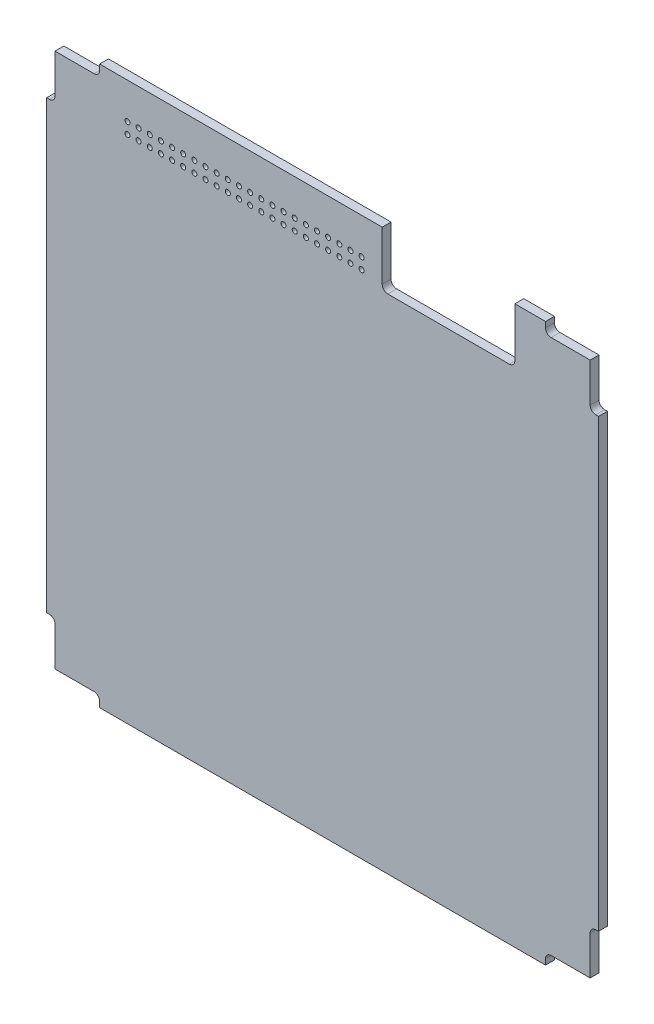
SolidWorks part; units mm, degrees
material "ABS"
ref_plane "Front Plane" through (0, 0, 0) normal (0, 0, 1) x (1, 0, 0)
ref_plane "Top Plane" through (0, 0, 0) normal (0, 1, 0) x (1, 0, 0)
ref_plane "Right Plane" through (0, 0, 0) normal (1, 0, 0) x (0, 0, -1)
sketch "Sketch1" plane through (0, 0, 0) normal (0, 0, 1) x (1, 0, 0)
  line L0 (-40, 50) -> (-40, 48)
  line L1 (-50, -50) -> (50, -50)
  line L2 (-50, -50) -> (-50, 50)
  line L3 (-50, 50) -> (50, 50)
  line L4 (50, -50) -> (50, 50)
  line L5 (-50, -50) -> (50, 50) construction
  line L6 (-50, 50) -> (50, -50) construction
  line L7 (-50, 50) -> (-40, 50)
  line L8 (-50, 50) -> (-50, 40)
  line L9 (-40, 48) -> (-48, 48)
  line L10 (-48, 48) -> (-48, 40)
  line L11 (50, 50) -> (40, 50)
  line L12 (50, 50) -> (50, 40)
  line L13 (-48, 40) -> (-50, 40)
  line L14 (50, 40) -> (48, 40)
  line L15 (-50, -50) -> (-37.8649, -50)
  line L16 (-50, -50) -> (-50, -37.8649)
  line L17 (50, 50) -> (50, 40)
  line L18 (50, 50) -> (40, 50)
  line L19 (50, -50) -> (41.5, -50)
  line L20 (50, -50) -> (50, -41.5)
  line L21 (48, 40) -> (48, 48)
  line L22 (48, 48) -> (40, 48)
  line L23 (40, 48) -> (40, 50)
  line L24 (40, -50) -> (40, -48)
  line L25 (50, -50) -> (40, -50)
  line L26 (50, -50) -> (50, -40)
  line L27 (40, -48) -> (48, -48)
  line L28 (48, -48) -> (48, -40)
  line L29 (48, -40) -> (50, -40)
  line L30 (-50, -40) -> (-48, -40)
  line L31 (-50, -50) -> (-50, -40)
  line L32 (-50, -50) -> (-40, -50)
  line L33 (-48, -40) -> (-48, -48)
  line L34 (-48, -48) -> (-40, -48)
  line L35 (-40, -48) -> (-40, -50)
  point P0 (0, 0)
  point P38 (0, 0)
  dimension "D1" = 100
  dimension "D2" = 100
  dimension "D3" = 2
  dimension "D4" = 10
  dimension "D5" = 4
extrude "Boss-Extrude1" add sketch "Sketch1" along normal blind 1.5875 contours L1 L4 L3 L2 region at (0, 0, 0)
fillet "Fillet1" radius 1 8 edges at (-48, -40, 0.7937) (-40, -48, 0.7937) (40, -48, 0.7937) (48, -40, 0.7937) (48, 40, 0.7937) (40, 48, 0.7937) (-40, 48, 0.7937) (-48, 40, 0.7937)
sketch "Sketch2" plane through (0, 0, 1.5875) normal (0, 0, 1) x (1, 0, 0)
  line L0 (0, 50) -> (0, -50) construction
  line L1 (-40, 50) -> (40, 50) construction
  line L2 (-40, -50) -> (40, -50) construction
  line L4 (-36, 45.8) -> (8, 45.8) construction
  line L5 (-36, 45.8) -> (-36, 43.55) construction
  line L6 (-36, 43.55) -> (8, 43.55) construction
  line L7 (8, 45.8) -> (8, 43.55) construction
  line L8 (-36, 50) -> (8, 50) construction
  line L9 (-36, 50) -> (-36, 45.8) construction
  line L10 (-36, 45.8) -> (8, 45.8) construction
  line L11 (8, 50) -> (8, 45.8) construction
  circle A0 centre (-35, 43.55) radius 0.45
  circle A1 centre (-33, 43.55) radius 0.45
  circle A2 centre (-31, 43.55) radius 0.45
  circle A3 centre (-29, 43.55) radius 0.45
  circle A4 centre (-27, 43.55) radius 0.45
  circle A5 centre (-25, 43.55) radius 0.45
  circle A6 centre (-23, 43.55) radius 0.45
  circle A7 centre (-21, 43.55) radius 0.45
  circle A8 centre (-19, 43.55) radius 0.45
  circle A9 centre (-17, 43.55) radius 0.45
  circle A10 centre (-15, 43.55) radius 0.45
  circle A11 centre (-13, 43.55) radius 0.45
  circle A12 centre (-11, 43.55) radius 0.45
  circle A13 centre (-9, 43.55) radius 0.45
  circle A14 centre (-7, 43.55) radius 0.45
  circle A15 centre (-5, 43.55) radius 0.45
  circle A16 centre (-3, 43.55) radius 0.45
  circle A17 centre (-1, 43.55) radius 0.45
  circle A18 centre (1, 43.55) radius 0.45
  circle A19 centre (3, 43.55) radius 0.45
  circle A20 centre (5, 43.55) radius 0.45
  circle A21 centre (7, 43.55) radius 0.45
  circle A22 centre (-33, 41.55) radius 0.45
  circle A23 centre (-31, 41.55) radius 0.45
  circle A24 centre (-29, 41.55) radius 0.45
  circle A25 centre (-27, 41.55) radius 0.45
  circle A26 centre (-25, 41.55) radius 0.45
  circle A27 centre (-23, 41.55) radius 0.45
  circle A28 centre (-21, 41.55) radius 0.45
  circle A29 centre (-19, 41.55) radius 0.45
  circle A30 centre (-17, 41.55) radius 0.45
  circle A31 centre (-15, 41.55) radius 0.45
  circle A32 centre (-13, 41.55) radius 0.45
  circle A33 centre (-11, 41.55) radius 0.45
  circle A34 centre (-9, 41.55) radius 0.45
  circle A35 centre (-7, 41.55) radius 0.45
  circle A36 centre (-5, 41.55) radius 0.45
  circle A37 centre (-3, 41.55) radius 0.45
  circle A38 centre (-1, 41.55) radius 0.45
  circle A39 centre (1, 41.55) radius 0.45
  circle A40 centre (3, 41.55) radius 0.45
  circle A41 centre (5, 41.55) radius 0.45
  circle A42 centre (7, 41.55) radius 0.45
  circle A43 centre (-35, 41.55) radius 0.45
  dimension "D1" = 0.9
  dimension "D6" = 15
  dimension "D4" = 42
  dimension "D5" = 2
  dimension "D7" = 2.25
  dimension "D8" = 44
  dimension "D10" = 1
  dimension "D11" = 4.2
  dimension "D2" = 22
  dimension "D3" = 2
extrude "Cut-Extrude1" cut sketch "Sketch2" against normal through all
sketch "Sketch3" plane through (0, 50, 0) normal (0, 1, 0) x (1, 0, 0)
  line L0 (-40, 0) -> (40, 0) construction
  line L1 (10.7, 0) -> (19.7, 0)
  line L2 (10.7, 0) -> (10.7, -1.5875)
  line L3 (10.7, -1.5875) -> (19.7, -1.5875)
  line L5 (-40, -1.5875) -> (40, -1.5875) construction
  line L6 (15.2, 0) -> (15.2, -1.5875) construction
  line L7 (12, 0) -> (12, -1.5875) construction
  line L8 (18.4, 0) -> (18.4, -1.5875) construction
  line L9 (-40, -1.5875) -> (40, -1.5875) construction
  line L10 (7, 0) -> (7, -1.5875) construction
  line L11 (6.55, -1.5875) -> (7.45, -1.5875) construction
  line L12 (19.7, 0) -> (34.5, 0)
  line L14 (19.7, -1.5875) -> (34.5, -1.5875)
  line L15 (34.5, 0) -> (34.5, -1.5875)
  dimension "D1" = 9
  dimension "D2" = 6.4
  dimension "D3" = 3.2
  dimension "D4" = 5
  dimension "D5" = 14.8
extrude "Cut-Extrude2" cut sketch "Sketch3" against normal blind 9.8806
fillet "Fillet2" radius 1 2 edges at (10.7, 40.1194, 0.7938) (34.5, 40.1194, 0.7937)
sketch "Sketch5" plane through (0, 0, 0) normal (0, 0, -1) x (-1, 0, 0)
  line L0 (40, -50) -> (-40, -50) construction
  line L1 (-49.5, 50) -> (49.5, 50)
  line L2 (-49.5, 50) -> (-49.5, -50)
  line L3 (-49.5, -50) -> (49.5, -50)
  line L4 (49.5, 50) -> (49.5, -50)
  line L5 (40, 50) -> (-10.7, 50) construction
  line L6 (50, -40) -> (50, 40) construction
  dimension "D1" = 99
  dimension "D2" = 0.5
extrude "Cut-Extrude3" cut sketch "Sketch5" against normal through all flip side to cut
